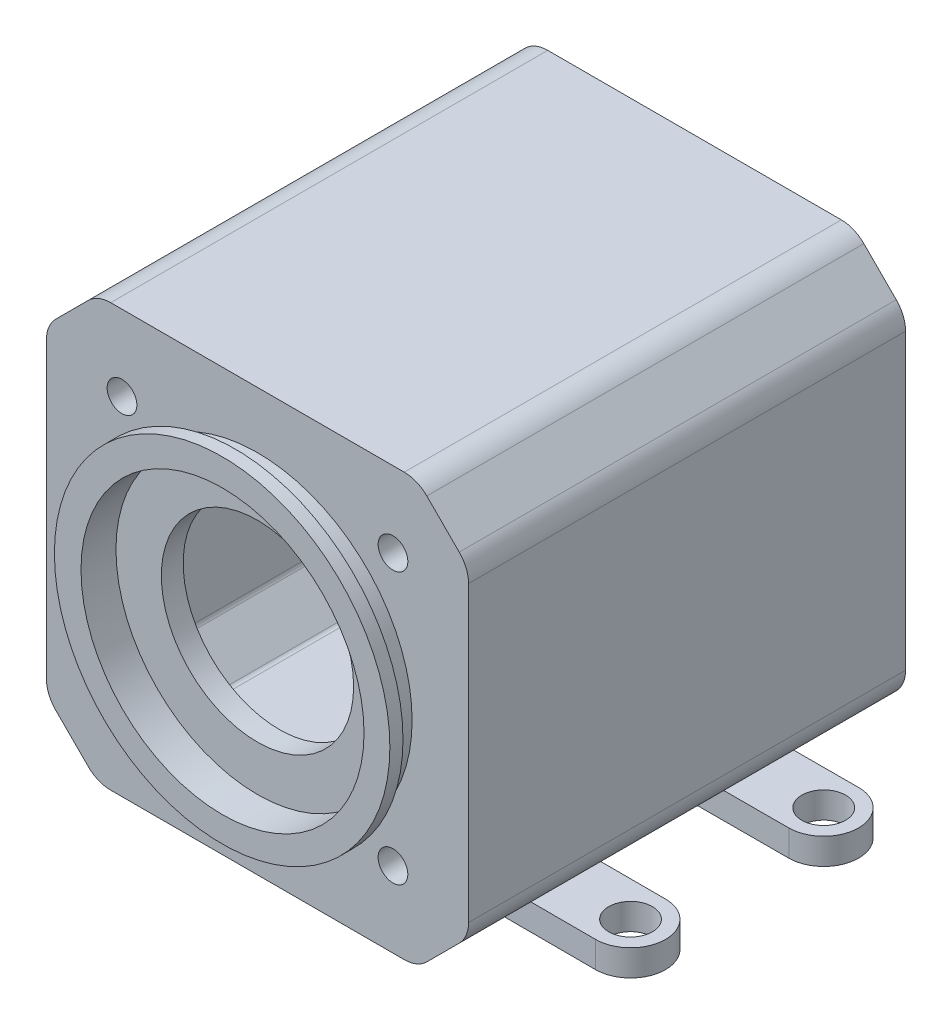
SolidWorks part; units mm, degrees
ref_plane "Alzado" through (0, 0, 0) normal (0, 0, 1) x (1, 0, 0)
ref_plane "Planta" through (0, 0, 0) normal (0, 1, 0) x (1, 0, 0)
ref_plane "Vista lateral" through (0, 0, 0) normal (1, 0, 0) x (0, 0, -1)
sketch "Croquis37" plane through (0, 0, 0) normal (0, 0, 1) x (1, 0, 0)
  line L0 (16.836, -21.2356) -> (-16.7498, -21.2356)
  line L1 (-17.2094, -21.0453) -> (-20.9165, -17.3381)
  line L2 (-21.1069, -16.8785) -> (-21.1069, 16.7073)
  line L3 (-20.9165, 17.1669) -> (-17.2094, 20.874)
  line L4 (-16.7498, 21.0644) -> (16.836, 21.0644)
  line L5 (17.2956, 20.874) -> (21.0027, 17.1669)
  line L6 (21.1931, 16.7073) -> (21.1931, -16.8785)
  line L7 (21.0027, -17.3381) -> (17.2956, -21.0453)
  line L8 (-24.1069, -16.8785) -> (-24.1069, 16.7073)
  line L9 (-23.0379, 19.2882) -> (-19.3308, 22.9953)
  line L10 (-16.7498, 24.0644) -> (16.836, 24.0644)
  line L11 (19.4169, 22.9953) -> (23.124, 19.2882)
  line L12 (24.1931, 16.7073) -> (24.1931, -16.8785)
  line L13 (23.124, -19.4595) -> (19.4169, -23.1666)
  line L14 (16.836, -24.2356) -> (-16.7498, -24.2356)
  line L15 (-19.3308, -23.1666) -> (-23.0379, -19.4595)
  arc A0 (-17.2094, -21.0453) -> (-16.7498, -21.2356) centre (-16.7498, -20.5856) ccw
  arc A1 (-21.1069, -16.8785) -> (-20.9165, -17.3381) centre (-20.4569, -16.8785) ccw
  arc A2 (-20.9165, 17.1669) -> (-21.1069, 16.7073) centre (-20.4569, 16.7073) ccw
  arc A3 (-16.7498, 21.0644) -> (-17.2094, 20.874) centre (-16.7498, 20.4144) ccw
  arc A4 (17.2956, 20.874) -> (16.836, 21.0644) centre (16.836, 20.4144) ccw
  arc A5 (21.1931, 16.7073) -> (21.0027, 17.1669) centre (20.5431, 16.7073) ccw
  arc A6 (21.0027, -17.3381) -> (21.1931, -16.8785) centre (20.5431, -16.8785) ccw
  arc A7 (16.836, -21.2356) -> (17.2956, -21.0453) centre (16.836, -20.5856) ccw
  circle A8 centre (-15.4569, -15.5856) radius 1.7
  circle A9 centre (15.5431, -15.5856) radius 1.7
  circle A10 centre (-15.4569, 15.4144) radius 1.7
  circle A11 centre (15.5431, 15.4144) radius 1.7
  circle A12 centre (0.0431, -0.0856) radius 11
  arc A13 (-23.0379, 19.2882) -> (-24.1069, 16.7073) centre (-20.4569, 16.7073) ccw
  arc A14 (-16.7498, 24.0644) -> (-19.3308, 22.9953) centre (-16.7498, 20.4144) ccw
  arc A15 (19.4169, 22.9953) -> (16.836, 24.0644) centre (16.836, 20.4144) ccw
  arc A16 (24.1931, 16.7073) -> (23.124, 19.2882) centre (20.5431, 16.7073) ccw
  arc A17 (23.124, -19.4595) -> (24.1931, -16.8785) centre (20.5431, -16.8785) ccw
  arc A18 (16.836, -24.2356) -> (19.4169, -23.1666) centre (16.836, -20.5856) ccw
  arc A19 (-19.3308, -23.1666) -> (-16.7498, -24.2356) centre (-16.7498, -20.5856) ccw
  arc A20 (-24.1069, -16.8785) -> (-23.0379, -19.4595) centre (-20.4569, -16.8785) ccw
  dimension "D1" = 3
extrude "Saliente-Extruir3" add sketch "Croquis37" against normal blind 50 contours L8 A20 L15 A19 L14 A18 L13 A17 L12 A16 L11 A15 L10 A14 L9 A13 A7 L0 A0 L1 A1 L2 A2 L3 A3 L4 A4 L5 A5 L6 A6 L7 region at (-23.4239, -0.0856, 0)
extrude "Saliente-Extruir4" add sketch "Croquis37<3>" against normal blind 2.5 separate body contours L0 A7 L7 A6 L6 A5 L5 A4 L4 A3 L3 A2 L2 A1 L1 A0 A12 A11 A10 A9 A8 region at (0.0431, -20.6374, 0)
sketch "Croquis37<3>" plane through (0, 0, 0) normal (0, 0, 1) x (1, 0, 0) same geometry as "Croquis37"
sketch "Croquis38" plane through (0, 0, 0) normal (0, 0, 1) x (1, 0, 0)
  circle A1 centre (0.0431, -0.0856) radius 16.19
  circle A3 centre (0.0431, -0.0856) radius 17.69
  dimension "D1" = 32.38
  dimension "D2" = 35.38
extrude "Saliente-Extruir5" add sketch "Croquis38" along normal blind 4
sketch "Croquis40" plane through (0, 0, 4) normal (0, 0, 1) x (1, 0, 0)
  circle A2 centre (0, 0) radius 19.19
  circle A3 centre (0.0431, -0.0856) radius 17.69 construction
  circle A4 centre (0.0431, -0.0856) radius 17.69
  dimension "D1" = 38.38
extrude "Saliente-Extruir6" add sketch "Croquis40" against normal blind 1.5
sketch "Croquis41" plane through (0, -24.2356, 0) normal (0, -1, 0) x (1, 0, 0)
  line L0 (16.836, -50) -> (-16.7498, -50) construction
  line L1 (-9.2048, -50) -> (9.2952, -50)
  line L2 (-9.2048, -50) -> (-9.2048, -39.5)
  line L3 (-9.2048, -39.5) -> (9.2952, -39.5)
  line L4 (9.2952, -50) -> (9.2952, -39.5)
  line L7 (-16.7498, -50) -> (-16.7498, 0) construction
  dimension "D1" = 18.5
  dimension "D2" = 10.5
  dimension "D3" = 7.545
extrude "Cortar-Extruir1" cut sketch "Croquis41" against normal blind 11.5
sketch "Croquis42" plane through (0, -24.2356, 0) normal (0, -1, 0) x (1, 0, 0)
  line L0 (-16.7498, 0) -> (16.836, 0) construction
  line L1 (0, 0) -> (0.0431, -50) construction
  line L2 (-16.7498, -50) -> (16.836, -50) construction
  line L3 (-16.7498, 0) -> (-16.7498, -10) construction
  line L4 (-16.7498, -50) -> (-16.7498, 0) construction
  line L5 (0.0215, -25) -> (-24.1069, -25) construction
  line L6 (-16.7498, -10) -> (-28.7498, -10)
  line L7 (-16.7498, -10) -> (-16.7498, -18)
  line L8 (-16.7498, -18) -> (-28.7498, -18)
  line L10 (-24.1069, -50) -> (-24.1069, 0) construction
  line L11 (-24.1069, -25) -> (24.1931, -25) construction
  line L12 (24.1931, -50) -> (24.1931, 0) construction
  line L13 (16.767, -9.9711) -> (16.7808, -17.9711)
  line L14 (16.7808, -17.9711) -> (28.7808, -17.9504)
  line L15 (16.767, -9.9711) -> (28.767, -9.9504)
  line L16 (-16.7498, -40) -> (-28.7498, -40)
  line L17 (-16.7498, -40) -> (-16.7498, -32)
  line L18 (-16.7498, -32) -> (-28.7498, -32)
  line L19 (16.767, -40.0289) -> (16.7808, -32.0289)
  line L20 (16.7808, -32.0289) -> (28.7808, -32.0496)
  line L21 (16.767, -40.0289) -> (28.767, -40.0496)
  arc A0 (-28.7498, -10) -> (-28.7498, -18) centre (-28.7498, -14) ccw
  arc A1 (28.767, -9.9504) -> (28.7808, -17.9504) centre (28.7739, -13.9504) cw
  arc A2 (-28.7498, -40) -> (-28.7498, -32) centre (-28.7498, -36) cw
  arc A3 (28.767, -40.0496) -> (28.7808, -32.0496) centre (28.7739, -36.0496) ccw
  dimension "D4" = 8
  dimension "D1" = 10
  dimension "D2" = 8
extrude "Saliente-Extruir7" add sketch "Croquis42" against normal blind 3
sketch "Croquis44" plane through (0, -21.2356, 0) normal (0, 1, 0) x (1, 0, 0)
  circle A0 centre (-28.7498, 36) radius 2.5
  circle A1 centre (28.7739, 36.0496) radius 2.5
  circle A2 centre (28.7739, 13.9504) radius 2.5
  circle A3 centre (-28.7498, 14) radius 2.5
  dimension "D1" = 5
  dimension "D2" = 5
  dimension "D3" = 5
  dimension "D4" = 5
extrude "Cortar-Extruir2" cut sketch "Croquis44" against normal blind 3
